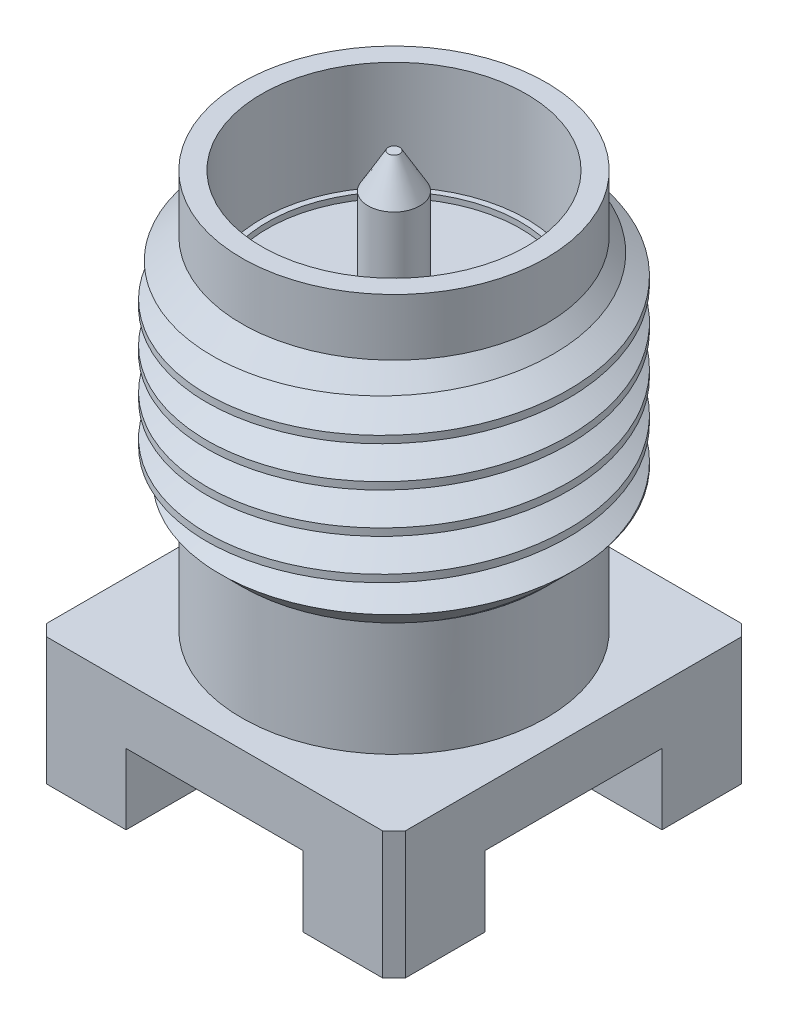
SolidWorks part; units mm, degrees
ref_plane "Спереди" through (0, 0, 0) normal (0, 0, 1) x (1, 0, 0)
ref_plane "Сверху" through (0, 0, 0) normal (0, 1, 0) x (1, 0, 0)
ref_plane "Справа" through (0, 0, 0) normal (1, 0, 0) x (0, 0, -1)
sketch "Эскиз1" plane through (0, 0, 0) normal (0, 0, 1) x (1, 0, 0)
  line L2 (-2.675, 2.27) -> (-2.675, 4.27)
  line L3 (-2.675, 4.27) -> (-3.175, 4.77)
  line L4 (-3.175, 4.77) -> (-3.175, 7.77)
  line L5 (-3.175, 7.77) -> (-2.675, 8.27)
  line L6 (-2.675, 8.27) -> (-2.675, 9.27)
  line L7 (-2.675, 9.27) -> (-2.325, 9.27)
  line L8 (-2.325, 9.27) -> (-2.325, 7.37)
  line L9 (-2.325, 7.37) -> (-2.225, 7.37)
  line L10 (-2.225, 7.37) -> (-2.225, 7.27)
  line L11 (-2.225, 7.27) -> (-0.455, 7.27)
  line L12 (-0.455, 7.27) -> (-0.455, 8.9551)
  line L13 (-0.455, 8.9551) -> (-0.1, 9.57)
  line L14 (-0.1, 9.57) -> (0, 9.57)
  line L15 (-2.675, 2.27) -> (-0.635, 2.27)
  line L16 (0, 6.9) -> (0, 9.57)
  line L18 (0, 0) -> (0, 6.9)
  line L19 (0, 0) -> (-0.635, 0)
  line L20 (-0.635, 0) -> (-0.635, 2.27)
  line L21 (0, -1000) -> (0, 49000) construction
  dimension "D2" = 6.35
  dimension "D3" = 2
  dimension "D4" = 45
  dimension "D5" = 2.27
  dimension "D6" = 1
  dimension "D7" = 4.65
  dimension "D8" = 2
  dimension "D9" = 0.455
  dimension "D10" = 1.9
  dimension "D11" = 0.1
  dimension "D12" = 0.3
  dimension "D13" = 30
  dimension "D14" = 0.2
  dimension "D15" = 5.35
  dimension "D16" = 1.27
  dimension "D17" = 7
revolve "Повернуть1" add sketch "Эскиз1" angle 360 about L21
sketch "Эскиз2" plane through (0, 2.27, 0) normal (0, -1, 0) x (1, 0, 0)
  line L0 (2.955, -3.155) -> (3.155, -2.955)
  line L1 (-2.955, -3.155) -> (2.955, -3.155)
  line L2 (-3.155, -2.955) -> (-3.155, 2.955)
  line L3 (-2.955, 3.155) -> (2.955, 3.155)
  line L4 (3.155, -2.955) -> (3.155, 2.955)
  line L5 (-3.155, -3.155) -> (3.155, 3.155) construction
  line L6 (-3.155, 3.155) -> (3.155, -3.155) construction
  line L7 (3.155, 2.955) -> (2.955, 3.155)
  line L8 (-3.155, 2.955) -> (-2.955, 3.155)
  line L9 (-2.955, -3.155) -> (-3.155, -2.955)
  point P0 (0, 0)
  dimension "D1" = 6.31
extrude "Бобышка-Вытянуть1" add sketch "Эскиз2" along normal blind 1
sketch "Эскиз5" plane through (0, 9.27, 0) normal (0, 1, 0) x (1, 0, 0)
  circle A0 centre (0, 0) radius 2.675
curve "Спираль1" pitch 0.705 height 5.64 radius 2.675 centre (0, 9.27, 0) axis (0, -1, 0) start towards (1, 0, 0)
sketch "Эскиз6" plane through (0, 0, 0) normal (0, 0, 1) x (1, 0, 0)
  line L0 (2.675, 9.27) -> (3.675, 8.6926)
  line L1 (3.675, 8.6926) -> (3.675, 9.8474)
  line L2 (3.675, 9.8474) -> (2.675, 9.27)
  line L3 (2.675, 9.27) -> (3.675, 9.27) construction
  point P6 (3.675, 9.27)
  dimension "D1" = 60
  dimension "D2" = 1
sweep "Вырез-По траектории1" cut profiles "Эскиз6" path "Спираль1" align with end faces yes
sketch "Sketch1" plane through (0, 1.27, 0) normal (0, -1, 0) x (-1, 0, 0)
  line L0 (1.5548, -3.155) -> (1.5548, -1.5548)
  line L1 (-2.955, -3.155) -> (2.955, -3.155) construction
  line L2 (1.5548, -1.5548) -> (3.155, -1.5548)
  line L3 (3.155, -2.955) -> (3.155, 2.955) construction
  line L4 (3.155, -1.5548) -> (3.155, -2.955)
  line L5 (3.155, -2.955) -> (2.955, -3.155)
  line L6 (2.955, -3.155) -> (1.5548, -3.155)
  dimension "D1" = 1.6002
  dimension "D2" = 1.6002
extrude "Boss-Extrude1" add sketch "Sketch1" along normal blind 1.24
pattern_circular "CirPattern1" count 4 every 90 about axis through (0, 0, 0) along (0, -1, 0) of "Boss-Extrude1"
